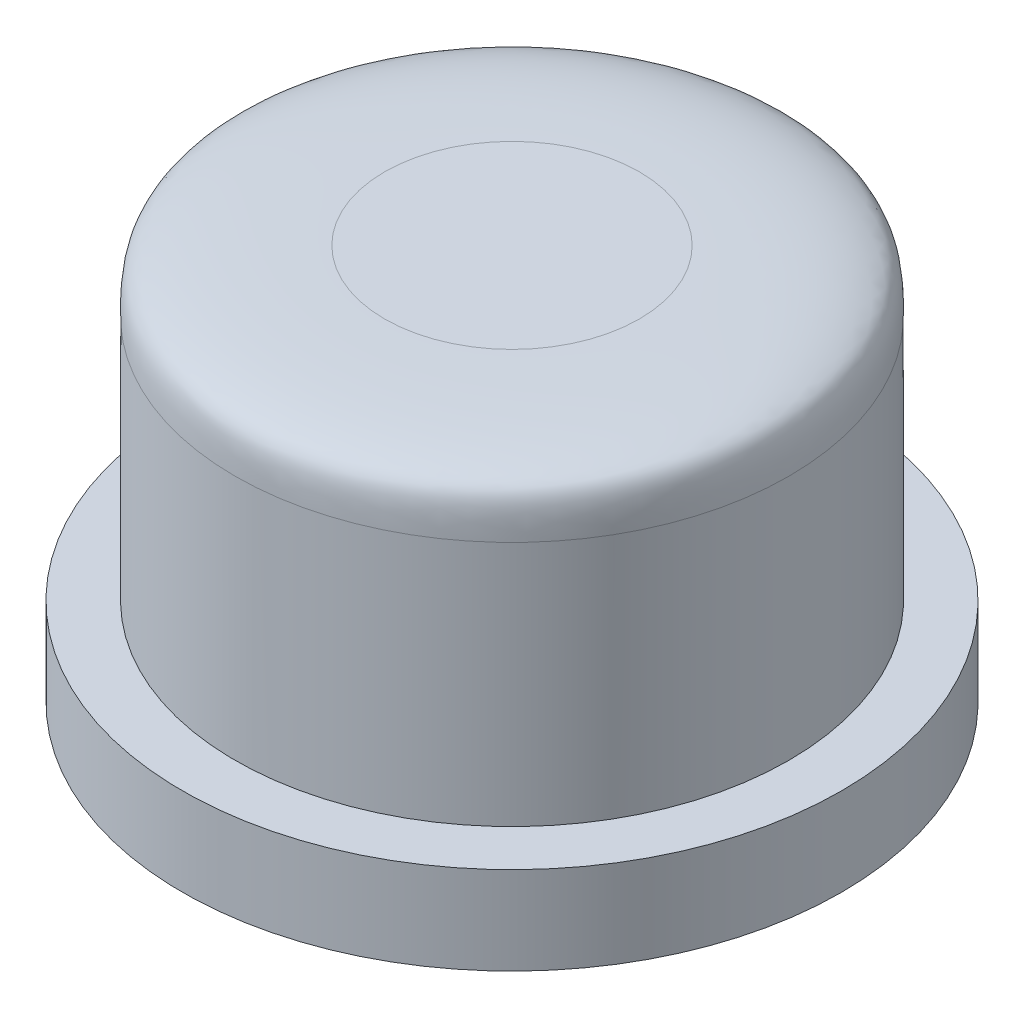
SolidWorks part; units mm, degrees
ref_plane "前视基准面" through (0, 0, 0) normal (0, 0, 1) x (1, 0, 0)
ref_plane "上视基准面" through (0, 0, 0) normal (0, 1, 0) x (1, 0, 0)
ref_plane "右视基准面" through (0, 0, 0) normal (1, 0, 0) x (0, 0, -1)
sketch "草图1" plane through (0, 0, 0) normal (0, 0, 1) x (1, 0, 0)
  line L0 (2.3, 0) -> (2.3, 0.9)
  line L1 (2.3, 0.9) -> (0, 0.9)
  line L2 (0, 0.9) -> (0, 4.5)
  line L3 (0, 4.5) -> (3.15, 4.5)
  line L5 (3.75, 0) -> (2.3, 0)
  line L6 (3.15, 4.5) -> (3.15, 1)
  line L7 (3.15, 1) -> (3.75, 1)
  line L8 (3.75, 1) -> (3.75, 0)
  dimension "D1" = 0.6
  dimension "D2" = 3.15
  dimension "D3" = 0.1
  dimension "D4" = 1
  dimension "D5" = 2.3
  dimension "D6" = 3.5
revolve "旋转1" add sketch "草图1" angle 360 about L2
sketch "草图2" plane through (0, 0, 0) normal (0, 0, 1) x (1, 0, 0)
  line L0 (3.15, 4.5) -> (-3.15, 4.5) construction
  line L1 (3.15, 1) -> (3.15, 4.5) construction
  line L4 (0, 4.5) -> (0, 2.4528) construction
  line L10 (1.45, 4.5) -> (3.15, 4.5)
  line L11 (3.15, 4.5) -> (3.15, 3.8)
  spline S0 degree 3 poles (1.45, 4.5) (2.3736, 4.5) (2.7696, 4.434) (3.1532, 4.2676) (3.15, 4.0259) (3.15, 3.8) knots 0 0 0 0 0.535445 0.635445 1 1 1 1
  dimension "D1" = 0.7
  dimension "D2" = 1.7
  dimension "D3" = 0.1469
revolve "切除-旋转6" cut sketch "草图2" angle 360 about L4
